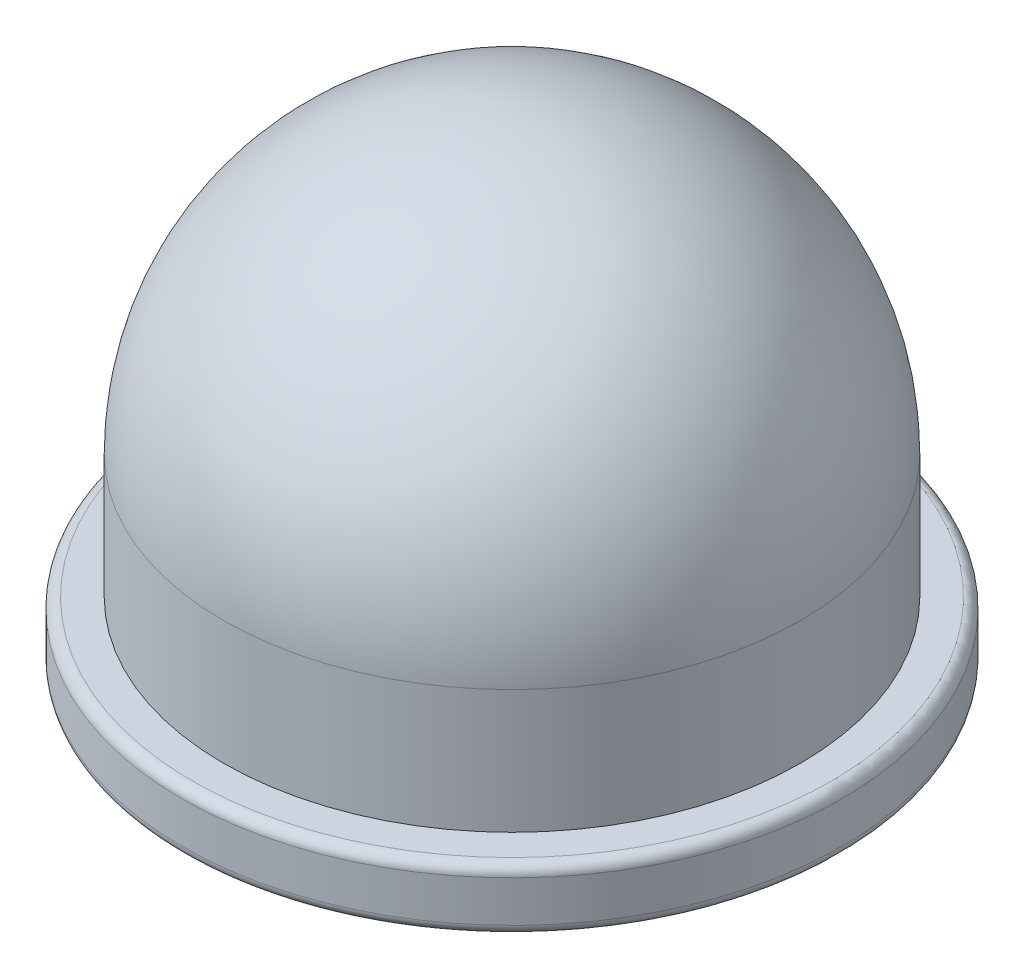
SolidWorks part; units mm, degrees
material "Rubber"
ref_plane "Front Plane" through (0, 0, 0) normal (0, 0, 1) x (1, 0, 0)
ref_plane "Top Plane" through (0, 0, 0) normal (0, 1, 0) x (1, 0, 0)
ref_plane "Right Plane" through (0, 0, 0) normal (1, 0, 0) x (0, 0, -1)
sketch "Sketch1" plane through (0, 0, 0) normal (0, 1, 0) x (1, 0, 0)
  circle A0 centre (0, 0) radius 7
  dimension "D1" = 14
extrude "Boss-Extrude1" add sketch "Sketch1" along normal blind 10
sketch "Sketch2" plane through (0, 0, 0) normal (0, -1, 0) x (1, 0, 0)
  circle A0 centre (0, 0) radius 8
  dimension "D1" = 16
extrude "Boss-Extrude2" add sketch "Sketch2" along normal blind 1.5
fillet "Fillet1" radius 7 1 edges at (0, 10, 7)
shell "Shell1" thickness 1.5 removed face at (0, -1.5, -8)
fillet "Fillet2" radius 0.25 2 edges at (0, -1.5, -8) (0, 0, -8)
